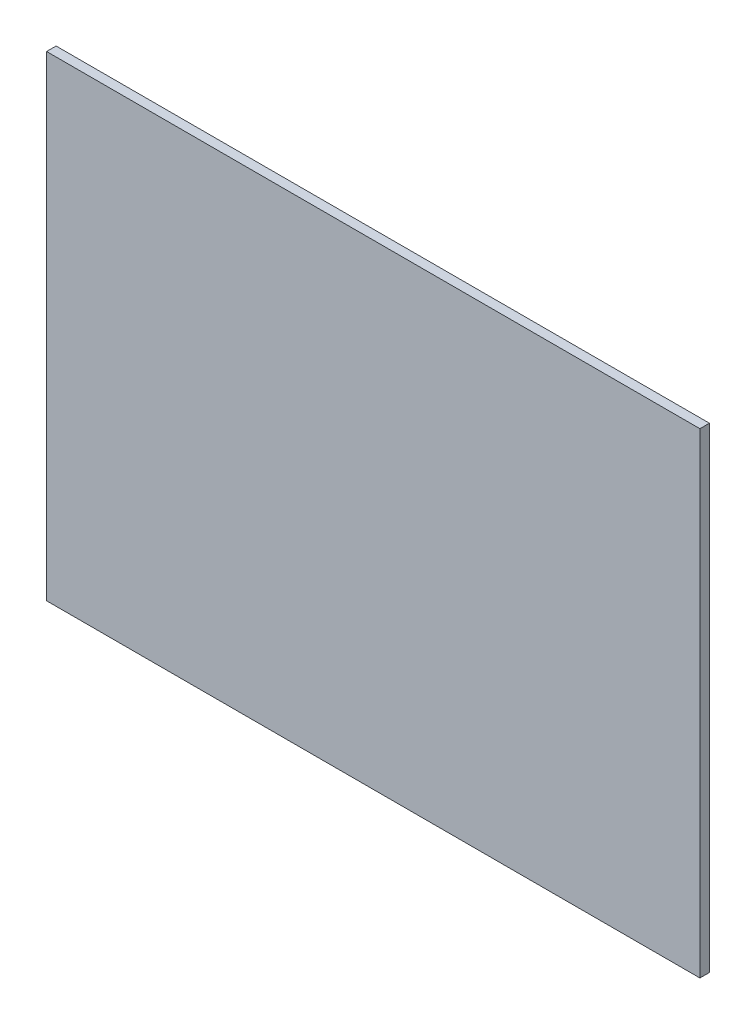
SolidWorks part; units mm, degrees
material "PET"
ref_plane "Front Plane" through (0, 0, 0) normal (0, 0, 1) x (1, 0, 0)
ref_plane "Top Plane" through (0, 0, 0) normal (0, 1, 0) x (1, 0, 0)
ref_plane "Right Plane" through (0, 0, 0) normal (1, 0, 0) x (0, 0, -1)
sketch "Sketch1" plane through (0, 0, 0) normal (0, 0, 1) x (1, 0, 0)
  line L1 (-28.5714, 277.1048) -> (383.4286, 277.1048)
  line L2 (-28.5714, 277.1048) -> (-28.5714, -22.8952)
  line L3 (-28.5714, -22.8952) -> (383.4286, -22.8952)
  line L4 (383.4286, 277.1048) -> (383.4286, -22.8952)
  dimension "D1" = 300
  dimension "D2" = 412
extrude "Boss-Extrude1" add sketch "Sketch1" along normal blind 6
